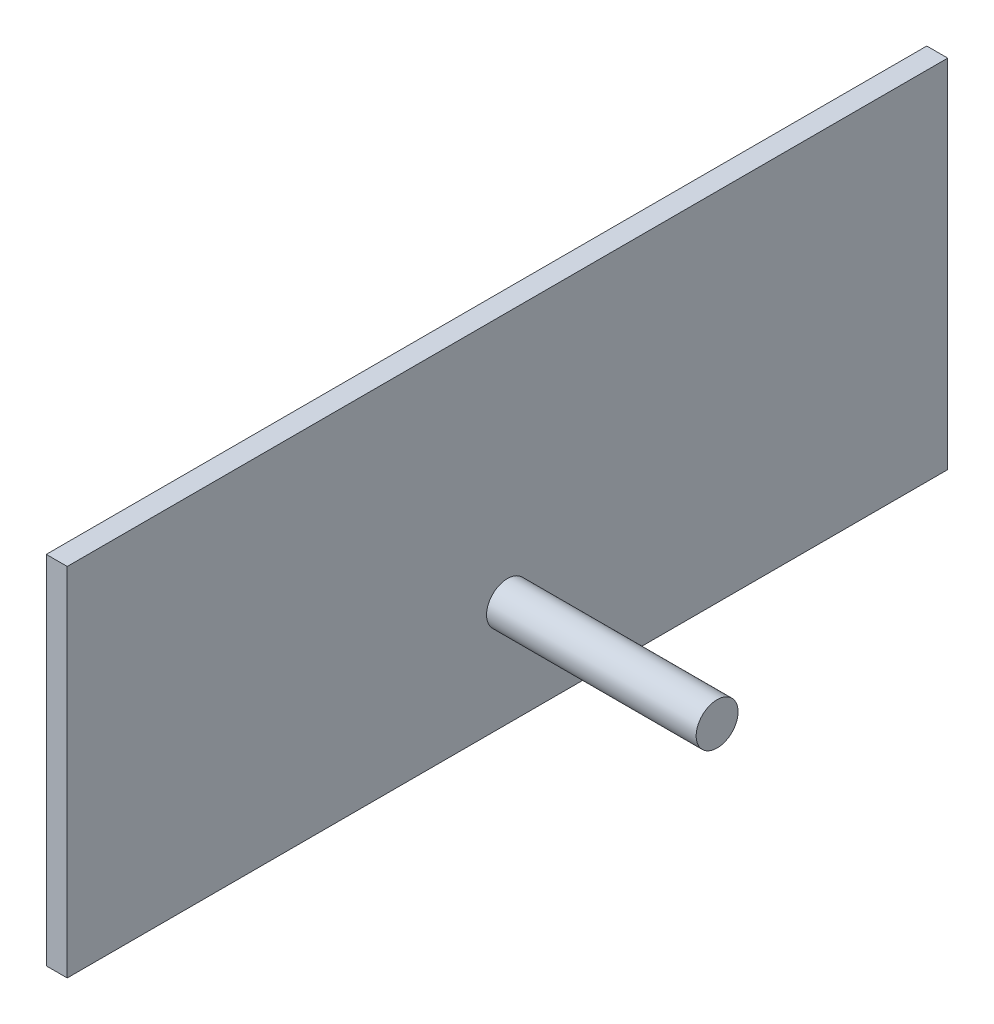
SolidWorks part; units mm, degrees
material "6061-T6 (SS)"
ref_plane "Front Plane" through (0, 0, 0) normal (0, 0, 1) x (1, 0, 0)
ref_plane "Top Plane" through (0, 0, 0) normal (0, 1, 0) x (1, 0, 0)
ref_plane "Right Plane" through (0, 0, 0) normal (1, 0, 0) x (0, 0, -1)
sketch "Sketch1" plane through (0, 0, 0) normal (1, 0, 0) x (0, 0, -1)
  line L4 (0, -25) -> (105, -25)
  line L5 (105, -25) -> (105, 0)
  line L6 (-105, 0) -> (-105, -25)
  line L7 (-105, -25) -> (0, -25)
  line L8 (-105, 0) -> (-105, 60)
  line L9 (-105, 60) -> (0, 60)
  line L10 (0, 60) -> (105, 60)
  line L11 (105, 60) -> (105, 0)
  circle A0 centre (0, 0) radius 5
extrude "Boss-Extrude1" add sketch "Sketch1" along normal blind 50 and the other way blind 5 contours A0
extrude "Boss-Extrude2" add sketch "Sketch1<3>" against normal blind 5 separate body
sketch "Sketch1<3>" plane through (0, 0, 0) normal (1, 0, 0) x (0, 0, -1) same geometry as "Sketch1"
